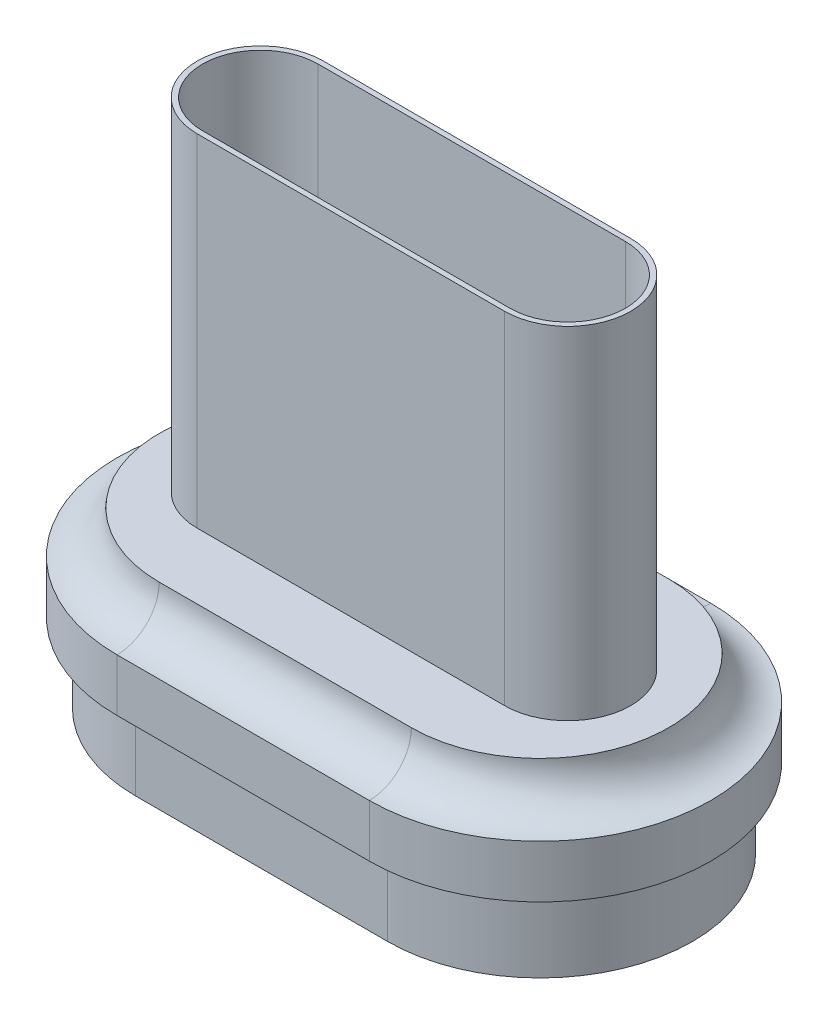
SolidWorks part; units mm, degrees
ref_plane "Front Plane" through (0, 0, 0) normal (0, 0, 1) x (1, 0, 0)
ref_plane "Top Plane" through (0, 0, 0) normal (0, 1, 0) x (1, 0, 0)
ref_plane "Right Plane" through (0, 0, 0) normal (1, 0, 0) x (0, 0, -1)
sketch "Sketch1" plane through (0, 0, 0) normal (0, 1, 0) x (1, 0, 0)
  line L0 (-2.4, 0) -> (2.4, 0) construction
  line L1 (-2.4, 2.9) -> (2.4, 2.9)
  line L2 (-2.4, -2.9) -> (2.4, -2.9)
  line L3 (-5.3, 0) -> (5.3, 0) construction
  line L4 (-2.4, 1.4) -> (2.4, 1.4)
  line L5 (-2.4, -1.4) -> (2.4, -1.4)
  line L6 (-2.4, 3.5) -> (2.4, 3.5) construction
  line L7 (-2.4, -3.5) -> (2.4, -3.5) construction
  arc A0 (-2.4, 2.9) -> (-2.4, -2.9) centre (-2.4, 0) ccw
  arc A1 (2.4, -2.9) -> (2.4, 2.9) centre (2.4, 0) ccw
  arc A2 (2.4, -1.4) -> (2.4, 1.4) centre (2.4, 0) ccw
  arc A3 (-2.4, 1.4) -> (-2.4, -1.4) centre (-2.4, 0) ccw
  arc A4 (2.4, -3.5) -> (2.4, 3.5) centre (2.4, 0) ccw construction
  arc A5 (-2.4, 3.5) -> (-2.4, -3.5) centre (-2.4, 0) ccw construction
  point P2 (0, 0)
  point P22 (-5.9, 0)
  point P23 (5.9, 0)
  dimension "D1" = 10.6
  dimension "D2" = 5.8
  dimension "D4" = 7
  dimension "D5" = 11.8
  dimension "D3" = 1.5
extrude "Boss-Extrude1" add sketch "Sketch1" along normal blind 1.5
sketch "Sketch2" plane through (0, 1.5, 0) normal (0, 1, 0) x (1, 0, 0)
  line L8 (-2.4, -3.25) -> (2.4, -3.25)
  line L9 (2.4, 3.25) -> (-2.4, 3.25)
  line L10 (-2.4, -3.25) -> (2.4, -3.25)
  line L11 (2.4, 3.25) -> (-2.4, 3.25)
  arc A6 (2.4, -3.25) -> (2.4, 3.25) centre (2.4, 0) ccw
  arc A7 (-2.4, 3.25) -> (-2.4, -3.25) centre (-2.4, 0) ccw
  arc A8 (2.4, -3.25) -> (2.4, 3.25) centre (2.4, 0) ccw
  arc A9 (-2.4, 3.25) -> (-2.4, -3.25) centre (-2.4, 0) ccw
  dimension "D1" = 0.35
extrude "Boss-Extrude2" add sketch "Sketch2" along normal blind 1
sketch "Sketch4" plane through (0, 2.5, 0) normal (0, 1, 0) x (1, 0, 0)
  line L6 (-2.4, -2.45) -> (2.4, -2.45)
  line L7 (2.4, 2.45) -> (-2.4, 2.45)
  line L8 (-2.4, -2.45) -> (2.4, -2.45)
  line L9 (2.4, 2.45) -> (-2.4, 2.45)
  arc A8 (2.4, -2.45) -> (2.4, 2.45) centre (2.4, 0) ccw
  arc A9 (-2.4, 2.45) -> (-2.4, -2.45) centre (-2.4, 0) ccw
  arc A10 (2.4, -2.45) -> (2.4, 2.45) centre (2.4, 0) ccw
  arc A11 (-2.4, 2.45) -> (-2.4, -2.45) centre (-2.4, 0) ccw
  dimension "D1" = 0.8
extrude "Boss-Extrude4" add sketch "Sketch4" along normal blind 0.8
sketch "Sketch3" plane through (0, 3.3, 0) normal (0, 1, 0) x (1, 0, 0)
  line L0 (-2.925, 1.2) -> (2.925, 1.2)
  line L1 (2.925, -1.2) -> (-2.925, -1.2)
  line L2 (-2.925, 0) -> (2.925, 0) construction
  line L3 (-2.925, 1.1) -> (2.925, 1.1)
  line L4 (2.925, -1.1) -> (-2.925, -1.1)
  arc A0 (2.925, 1.2) -> (2.925, -1.2) centre (2.925, 0) cw
  arc A1 (-2.925, -1.2) -> (-2.925, 1.2) centre (-2.925, 0) cw
  arc A2 (2.925, 1.1) -> (2.925, -1.1) centre (2.925, 0) cw
  arc A3 (-2.925, -1.1) -> (-2.925, 1.1) centre (-2.925, 0) cw
  point P5 (0, 0)
  point P7 (-4.125, 0)
  point P9 (4.125, 0)
  dimension "D1" = 2.4
  dimension "D2" = 8.25
  dimension "D3" = 0.1
extrude "Boss-Extrude3" add sketch "Sketch3" along normal blind 6.5
fillet "Fillet1" radius 0.8 4 edges at (-4.85, 2.5, 0) (0, 2.5, -2.45) (4.85, 2.5, 0) (0, 2.5, 2.45)
